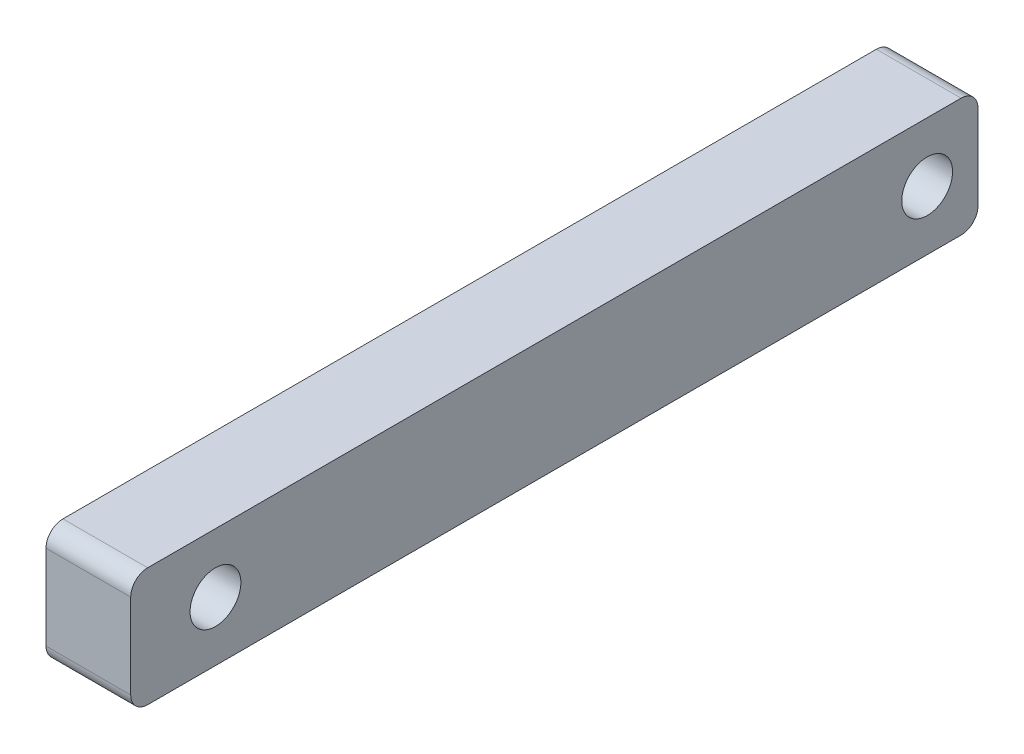
SolidWorks part; units mm, degrees
ref_plane "Alzado" through (0, 0, 0) normal (0, 0, 1) x (1, 0, 0)
ref_plane "Planta" through (0, 0, 0) normal (0, 1, 0) x (1, 0, 0)
ref_plane "Vista lateral" through (0, 0, 0) normal (1, 0, 0) x (0, 0, -1)
sketch "Croquis1" plane through (0, 0, 0) normal (1, 0, 0) x (0, 0, -1)
  line L0 (-24, 3.5) -> (24, 3.5)
  line L2 (-25, 0) -> (25, 0) construction
  line L3 (-25, 2.5) -> (-25, -2.5)
  line L4 (-24, -3.5) -> (24, -3.5)
  line L5 (25, 2.5) -> (25, -2.5)
  arc A0 (-25, -2.5) -> (-24, -3.5) centre (-24, -2.5) ccw
  arc A1 (-25, 2.5) -> (-24, 3.5) centre (-24, 2.5) cw
  arc A2 (24, -3.5) -> (25, -2.5) centre (24, -2.5) ccw
  arc A3 (24, 3.5) -> (25, 2.5) centre (24, 2.5) cw
  point P1 (0, 0)
  point P9 (-25, -3.5)
  point P13 (-25, 3.5)
  point P16 (25, -3.5)
  point P19 (25, 3.5)
  dimension "D3" = 1
  dimension "D4" = 1
  dimension "D1" = 3.5
  dimension "D2" = 50
extrude "Saliente-Extruir1" add sketch "Croquis1" along normal mid plane 5
sketch "Croquis2" plane through (0, 0, 0) normal (1, 0, 0) x (0, 0, -1)
  line L0 (-25, 2.5) -> (-25, -2.5) construction
  line L1 (25, -2.5) -> (25, 2.5) construction
  circle A0 centre (-20, 0) radius 1.5
  circle A1 centre (22, 0) radius 1.5
  dimension "D1" = 3
  dimension "D3" = 3
  dimension "D2" = 5
  dimension "D4" = 3
extrude "Cortar-Extruir1" cut sketch "Croquis2" against normal through all both and the other way through all
